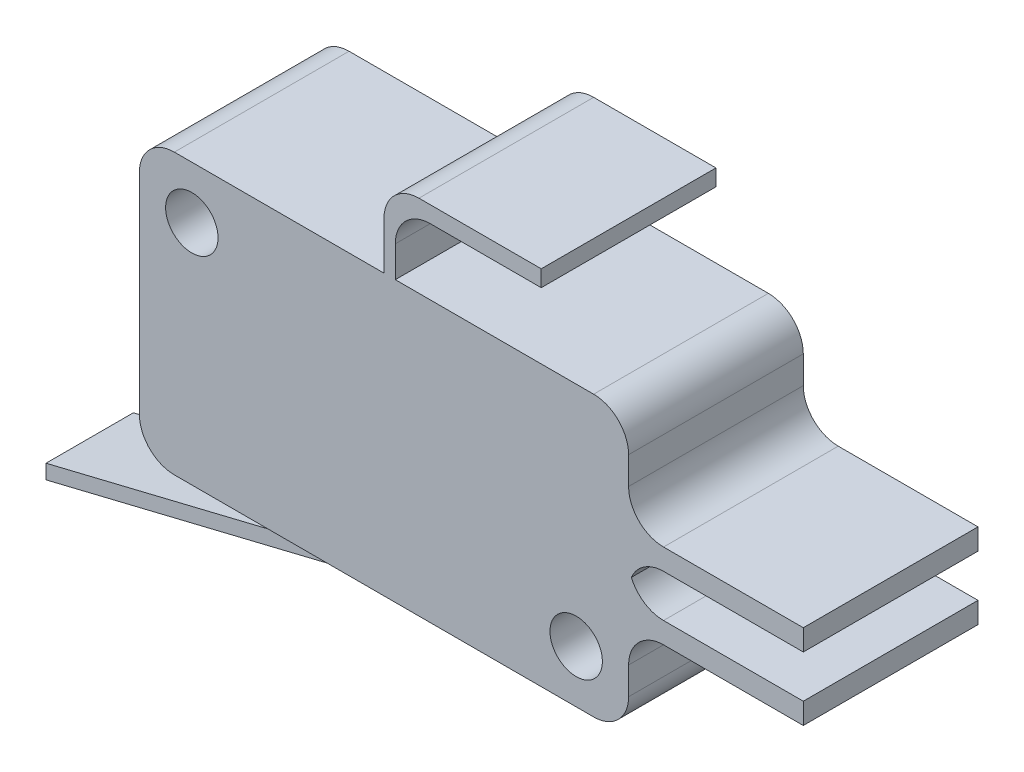
SolidWorks part; units mm, degrees
ref_plane "Front Plane" through (0, 0, 0) normal (0, 0, 1) x (1, 0, 0)
ref_plane "Top Plane" through (0, 0, 0) normal (0, 1, 0) x (1, 0, 0)
ref_plane "Right Plane" through (0, 0, 0) normal (1, 0, 0) x (0, 0, -1)
sketch "Sketch2" plane through (0, 0, 0) normal (0, 0, 1) x (1, 0, 0)
  line L0 (0, 8) -> (0, 12.7164)
  line L1 (14, -8) -> (3.4832, -8)
  line L2 (14, -8) -> (14, -2.4241)
  line L3 (14, 8) -> (0.6474, 8)
  line L4 (-14, -8) -> (-14, 8)
  line L5 (14, -8) -> (-14, 8) construction
  line L6 (14, 8) -> (-14, -8) construction
  line L7 (0, 12.7164) -> (9, 12.7164)
  line L8 (0.6474, 8) -> (0.6474, 11.7781)
  line L9 (0.6474, 11.7781) -> (9, 11.7781)
  line L10 (9, 11.7781) -> (9, 12.7164)
  line L11 (0, 8) -> (-14, 8)
  line L12 (0, 0) -> (7.7094, 0) construction
  line L13 (14, 2.4241) -> (24, 2.4241)
  line L14 (24, 2.4241) -> (24, 1.2187)
  line L15 (24, 1.2187) -> (14, 1.2187)
  line L16 (24, -1.2187) -> (14, -1.2187)
  line L17 (24, -2.4241) -> (24, -1.2187)
  line L18 (14, -2.4241) -> (24, -2.4241)
  line L19 (14, 2.4241) -> (14, 8)
  line L20 (14, -1.2187) -> (14, 1.2187)
  line L25 (3.4832, -8) -> (-14, -8)
  circle A1 centre (-11, 5) radius 1.5
  circle A2 centre (11, -5) radius 1.5
  point P0 (0, 0)
  point P27 (3.3618, -8)
  dimension "D3" = 3
  dimension "D4" = 3
  dimension "D5" = 3
  dimension "D6" = 3
  dimension "D7" = 3
  dimension "D1" = 16
  dimension "D2" = 28
  dimension "D8" = 9
  dimension "D9" = 10
extrude "Boss-Extrude1" add sketch "Sketch2" along normal blind 10
fillet "Fillet1" radius 2 10 edges at (14, -8, 5) (-14, -8, 5) (14, -1.2187, 5) (14, 1.2187, 5) (14, 2.4241, 5) (14, -2.4241, 5) (0.6474, 11.7781, 5) (14, 8, 5) (-14, 8, 5) (0, 12.7164, 5)
ref_plane "Plane1" through (0, 0, 5) normal (0, 0, -1) x (-1, 0, 0)
sketch "Sketch3" plane through (0, 0, 5) normal (0, 0, -1) x (-1, 0, 0)
  line L0 (-1.1092, -8) -> (-1.1092, -8.828)
  line L1 (12, -8) -> (-12, -8) construction
  line L2 (-1.1092, -8.828) -> (21.8468, -14.421)
  line L3 (21.8468, -14.421) -> (21.8468, -13.5942)
  line L4 (21.8468, -13.5942) -> (-1.1092, -8)
extrude "Boss-Extrude2" add sketch "Sketch3" along normal mid plane 5 separate body
fillet "Fillet2" radius 2 1 edges at (1.1092, -8.828, 5)
